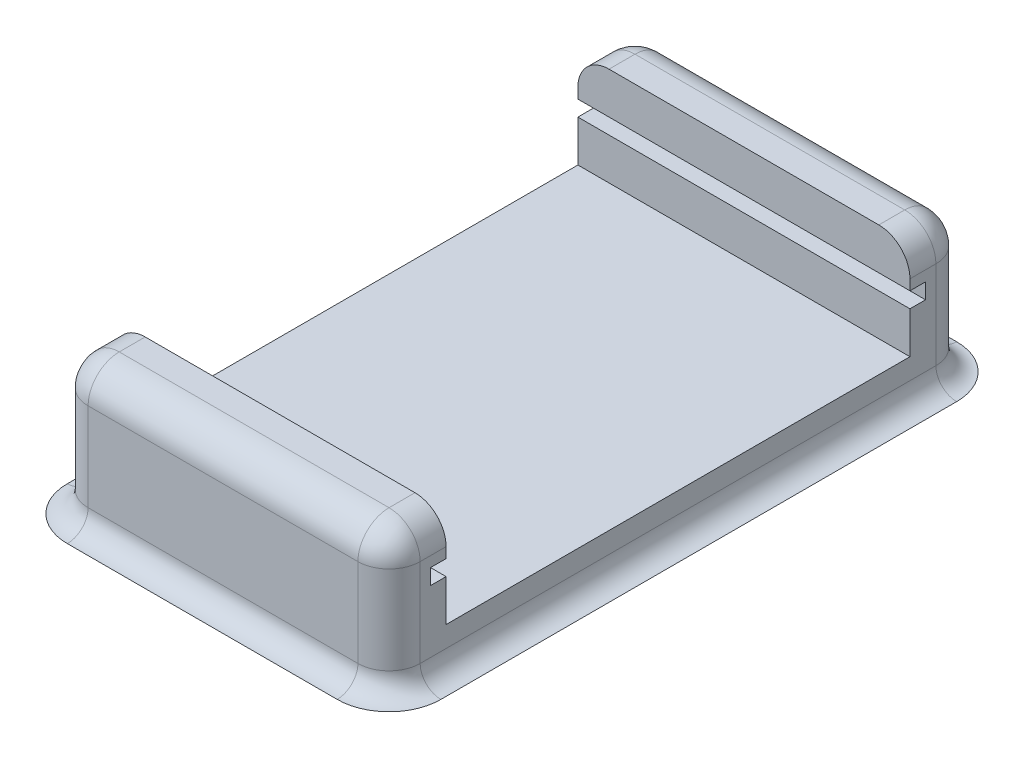
SolidWorks part; units mm, degrees
material "Melamine resin"
ref_plane "Front Plane" through (0, 0, 0) normal (0, 0, 1) x (1, 0, 0)
ref_plane "Top Plane" through (0, 0, 0) normal (0, 1, 0) x (1, 0, 0)
ref_plane "Right Plane" through (0, 0, 0) normal (1, 0, 0) x (0, 0, -1)
sketch "Sketch2" plane through (0, 0, 0) normal (0, 1, 0) x (1, 0, 0)
  line L1 (0, 0) -> (88.9, 0)
  line L2 (0, 0) -> (0, 152.4)
  line L3 (0, 152.4) -> (88.9, 152.4)
  line L10 (88.9, 152.4) -> (88.9, 0)
  dimension "D1" = 152.4
  dimension "D2" = 88.9
extrude "Boss-Extrude1" add sketch "Sketch2" along normal blind 5.9944 contours L3 L10 L1 L2
sketch "Sketch4" plane through (0, 5.9944, 0) normal (0, 1, 0) x (1, 0, 0)
  line L0 (0, 0) -> (0, 152.4) construction
  line L1 (0, 0) -> (88.9, 0) construction
  circle A0 centre (45.72, 109.8713) radius 2.7305
  circle A1 centre (45.72, 33.6713) radius 2.7305
  dimension "D3" = 5.461
  dimension "D4" = 5.461
  dimension "D1" = 76.2
  dimension "D2" = 45.72
  dimension "D5" = 33.6713
extrude "Cut-Extrude2" cut sketch "Sketch4" against normal through all both
sketch "Sketch5" plane through (0, 5.9944, 0) normal (0, 1, 0) x (1, 0, 0)
  line L0 (0, 152.4) -> (88.9, 152.4) construction
  line L1 (12.446, 15.748) -> (76.454, 15.748)
  line L2 (12.446, 15.748) -> (12.446, 2.54)
  line L3 (12.446, 2.54) -> (76.454, 2.54)
  line L4 (76.454, 15.748) -> (76.454, 2.54)
  line L5 (18.542, 7.62) -> (70.358, 7.62)
  line L6 (18.542, 7.62) -> (18.542, 15.748)
  line L7 (18.542, 15.748) -> (70.358, 15.748)
  line L8 (70.358, 7.62) -> (70.358, 15.748)
  line L9 (17.526, 13.208) -> (71.374, 13.208)
  line L10 (17.526, 13.208) -> (17.526, 11.43)
  line L11 (17.526, 11.43) -> (71.374, 11.43)
  line L12 (71.374, 13.208) -> (71.374, 11.43)
  line L13 (0, 0) -> (88.9, 0) construction
  point P16 (44.45, 152.4)
  point P17 (44.45, 15.748)
  dimension "D1" = 53.848
  dimension "D2" = 1.016
  dimension "D3" = 1.016
  dimension "D4" = 3.81
  dimension "D5" = 2.54
  dimension "D6" = 5.08
  dimension "D7" = 5.08
  dimension "D8" = 1.778
  dimension "D9" = 2.54
  dimension "D10" = 5.08
extrude "Boss-Extrude2" add sketch "Sketch5" along normal blind 101.6 contours L9 L12 L11 L8 L5 L6 L10 L1 L2 L3 L4 region at (44.45, 5.9944, -6.5736)
fillet "Fillet1" radius 3.81 4 edges at (12.446, 56.7944, -2.54) (12.446, 56.7944, -15.748) (76.454, 56.7944, -2.54) (76.454, 56.7944, -15.748)
fillet "Fillet2" radius 2.54 9 edges at (17.399, 5.9944, -15.748) (13.5619, 5.9944, -14.6321) (12.446, 5.9944, -9.144) (13.5619, 5.9944, -3.6559) (71.501, 5.9944, -15.748) (75.3381, 5.9944, -14.6321) (76.454, 5.9944, -9.144) (75.3381, 5.9944, -3.6559) (44.45, 5.9944, -2.54)
ref_plane "Plane1" through (44.45, 0, 0) normal (-1, 0, 0) x (0, 0, 1)
sketch "Sketch6" plane through (44.45, 0, 0) normal (-1, 0, 0) x (0, 0, 1)
  line L0 (0, 5.9944) -> (-152.4, 5.9944) construction
  line L1 (0, 5.9944) -> (-152.4, 5.9944)
  line L3 (-149.86, 5.9944) -> (-79.121, 5.9944)
  line L4 (-149.86, 5.9944) -> (-149.86, 23.1394)
  line L5 (-149.86, 23.1394) -> (-79.121, 23.1394)
  line L6 (-79.121, 5.9944) -> (-79.121, 23.1394)
  line L7 (-142.875, 23.1394) -> (-86.106, 23.1394)
  line L8 (-142.875, 23.1394) -> (-142.875, 11.0744)
  line L9 (-142.875, 11.0744) -> (-86.106, 11.0744)
  line L10 (-86.106, 23.1394) -> (-86.106, 11.0744)
  line L11 (-144.78, 18.0594) -> (-84.201, 18.0594)
  line L12 (-144.78, 18.0594) -> (-144.78, 16.1544)
  line L13 (-144.78, 16.1544) -> (-84.201, 16.1544)
  line L14 (-84.201, 18.0594) -> (-84.201, 16.1544)
  line L15 (-152.4, 5.9944) -> (-152.4, 0) construction
  dimension "D1" = 60.579
  dimension "D2" = 1.905
  dimension "D3" = 1.905
  dimension "D4" = 1.905
  dimension "D5" = 5.08
  dimension "D6" = 5.08
  dimension "D7" = 5.08
  dimension "D8" = 5.08
  dimension "D9" = 5.08
  dimension "D10" = 2.54
extrude "Boss-Extrude3" add sketch "Sketch6" along normal mid plane 40.64 contours L11 L14 L13 L10 L9 L8 L12 L5 L4 L1 L6 region at (44.45, 6.7223, -114.4905)
fillet "Fillet3" radius 3.81 2 edges at (44.45, 23.1394, -79.121) (44.45, 23.1394, -149.86)
fillet "Fillet6" radius 3.81 12 edges at (24.13, 23.1394, -84.5185) (24.13, 22.0235, -80.2369) (64.77, 23.1394, -84.5185) (64.77, 22.0235, -80.2369) (64.77, 23.1394, -144.4625) (64.77, 22.0235, -148.7441) (24.13, 23.1394, -144.4625) (24.13, 22.0235, -148.7441) (24.13, 12.6619, -79.121) (64.77, 12.6619, -79.121) (64.77, 12.6619, -149.86) (24.13, 12.6619, -149.86)
fillet "Fillet7" radius 2.54 8 edges at (25.2459, 5.9944, -80.2369) (44.45, 5.9944, -79.121) (63.6541, 5.9944, -80.2369) (64.77, 5.9944, -114.4905) (63.6541, 5.9944, -148.7441) (44.45, 5.9944, -149.86) (25.2459, 5.9944, -148.7441) (24.13, 5.9944, -114.4905)
sketch "Sketch7" plane through (0, 5.9944, 0) normal (0, 1, 0) x (1, 0, 0)
  line L0 (0, 0) -> (16.256, 0) construction
  line L1 (0, 152.4) -> (2.54, 152.4)
  line L2 (0, 152.4) -> (0, 0)
  line L3 (0, 0) -> (2.54, 0)
  line L4 (2.54, 152.4) -> (2.54, 0)
  dimension "D1" = 2.54
extrude "Cut-Extrude3" cut sketch "Sketch7" against normal through all both
sketch "Sketch8" plane through (0, 0, 0) normal (0, -1, 0) x (1, 0, 0)
  line L4 (2.54, 0) -> (2.54, -152.4)
  line L5 (2.54, -152.4) -> (88.9, -152.4)
  line L6 (88.9, -152.4) -> (88.9, 0)
  line L7 (88.9, 0) -> (2.54, 0)
  line L8 (2.54, 0) -> (2.54, -152.4)
  line L9 (2.54, -152.4) -> (88.9, -152.4)
  line L10 (88.9, -152.4) -> (88.9, 0)
  line L11 (88.9, 0) -> (2.54, 0)
  dimension "D1" = 0
extrude "Cut-Extrude4" cut sketch "Sketch8" against normal up to surface (5.9944 mm away) up to face at (44.6087, 5.9944, -45.1326)
sketch "Sketch9" plane through (0, 5.9944, 0) normal (0, -1, 0) x (1, 0, 0)
  line L0 (21.59, -114.4905) -> (67.31, -114.4905) construction
  line L1 (21.59, -82.931) -> (21.59, -146.05) construction
  line L2 (67.31, -146.05) -> (67.31, -82.931) construction
  line L3 (44.45, -89.0905) -> (44.45, -114.4905) construction
  line L4 (44.45, -114.4905) -> (44.45, -139.8905) construction
  circle A0 centre (44.45, -89.0905) radius 0.7937
  circle A1 centre (44.45, -139.8905) radius 0.7937
  point P10 (44.45, -134.1479)
  point P12 (44.45, -114.4905)
  dimension "D1" = 1.5875
  dimension "D2" = 1.5875
  dimension "D3" = 50.8
extrude "Cut-Extrude5" cut sketch "Sketch9" against normal blind 3.175
equation "\"threaded_insert_hole\"=0.1472"
equation "\"th\"=1.25249"
